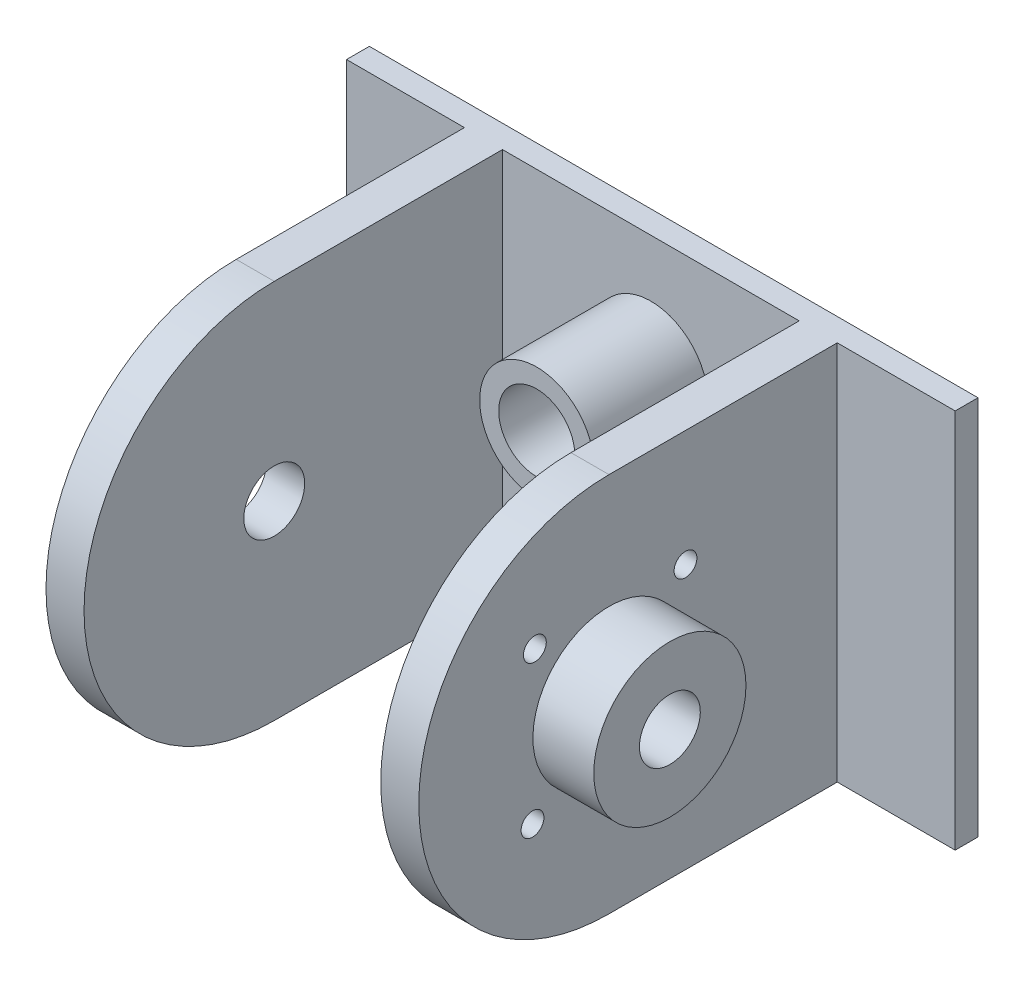
SolidWorks part; units mm, degrees
ref_plane "Front Plane" through (0, 0, 0) normal (0, 0, 1) x (1, 0, 0)
ref_plane "Top Plane" through (0, 0, 0) normal (0, 1, 0) x (1, 0, 0)
ref_plane "Right Plane" through (0, 0, 0) normal (1, 0, 0) x (0, 0, -1)
sketch "Sketch1" plane through (0, 0, 0) normal (0, 0, 1) x (1, 0, 0)
  line L1 (-24.5, 25) -> (24.5, 25)
  line L2 (-24.5, 25) -> (-24.5, -25)
  line L3 (-24.5, -25) -> (24.5, -25)
  line L4 (24.5, 25) -> (24.5, -25)
  dimension "D1" = 24.5
  dimension "D2" = 49
  dimension "D3" = 50
  dimension "D4" = 25
extrude "Boss-Extrude1" add sketch "Sketch1" along normal blind 3
sketch "Sketch2" plane through (0, 0, 3) normal (0, 0, 1) x (1, 0, 0)
  line L0 (-24.5, -25) -> (24.5, -25) construction
  line L1 (-24.5, 25) -> (-19.5, 25)
  line L2 (-24.5, 25) -> (-24.5, -25)
  line L3 (-24.5, -25) -> (-19.5, -25)
  line L4 (-19.5, 25) -> (-19.5, -25)
  line L6 (19.5, -25) -> (24.5, -25)
  line L7 (19.5, -25) -> (19.5, 25)
  line L8 (19.5, 25) -> (24.5, 25)
  line L9 (24.5, -25) -> (24.5, 25)
  dimension "D1" = 5
  dimension "D2" = 5
extrude "Boss-Extrude2" add sketch "Sketch2" along normal blind 55
sketch "Sketch3" plane through (-24.5, 0, 0) normal (-1, 0, 0) x (0, 0, 1)
  line L0 (58, 25) -> (58, -25) construction
  line L5 (0, 25) -> (0, -25)
  line L6 (0, -25) -> (58, -25)
  line L7 (58, -25) -> (58, 25)
  line L8 (58, 25) -> (0, 25)
  line L9 (0, 25) -> (0, -25)
  line L10 (0, -25) -> (33, -25)
  line L12 (33, 25) -> (0, 25)
  arc A0 (33, -25) -> (33, 25) centre (33, 0) ccw
  circle A1 centre (33, 0) radius 4
  dimension "D2" = 8
  dimension "D1" = 0
extrude "Cut-Extrude1" cut sketch "Sketch3" against normal through all flip side to cut
sketch "Sketch4" plane through (0, 0, 3) normal (0, 0, 1) x (1, 0, 0)
  line L0 (0, 0) -> (0, 22.9371) construction
  circle A0 centre (0, 10) radius 5
  circle A1 centre (0, 10) radius 7.5
  dimension "D1" = 15
  dimension "D2" = 10
extrude "Boss-Extrude3" add sketch "Sketch4" along normal blind 15
sketch "Sketch5" plane through (24.5, 0, 0) normal (1, 0, 0) x (0, 0, -1)
  circle A0 centre (-33, 0) radius 4 construction
  circle A1 centre (-33, 0) radius 4
  circle A2 centre (-33, 0) radius 10
extrude "Boss-Extrude4" add sketch "Sketch5" along normal blind 8
sketch "Sketch6" plane through (24.5, 0, 0) normal (1, 0, 0) x (0, 0, -1)
  circle A0 centre (-42.7442, 10.0524) radius 1.5
  circle A1 centre (-22.9476, 9.7442) radius 1.5
  circle A2 centre (-23.2558, -10.0524) radius 1.5
  circle A3 centre (-43.0524, -9.7442) radius 1.5
extrude "Cut-Extrude2" cut sketch "Sketch6" against normal up to next
sketch "Sketch7" plane through (0, 0, 0) normal (0, 0, -1) x (-1, 0, 0)
  line L1 (40, -25) -> (-40, -25)
  line L2 (40, -25) -> (40, 25)
  line L3 (40, 25) -> (-40, 25)
  line L4 (-40, -25) -> (-40, 25)
  dimension "D1" = 80
  dimension "D2" = 40
extrude "Boss-Extrude5" add sketch "Sketch7" against normal blind 3
